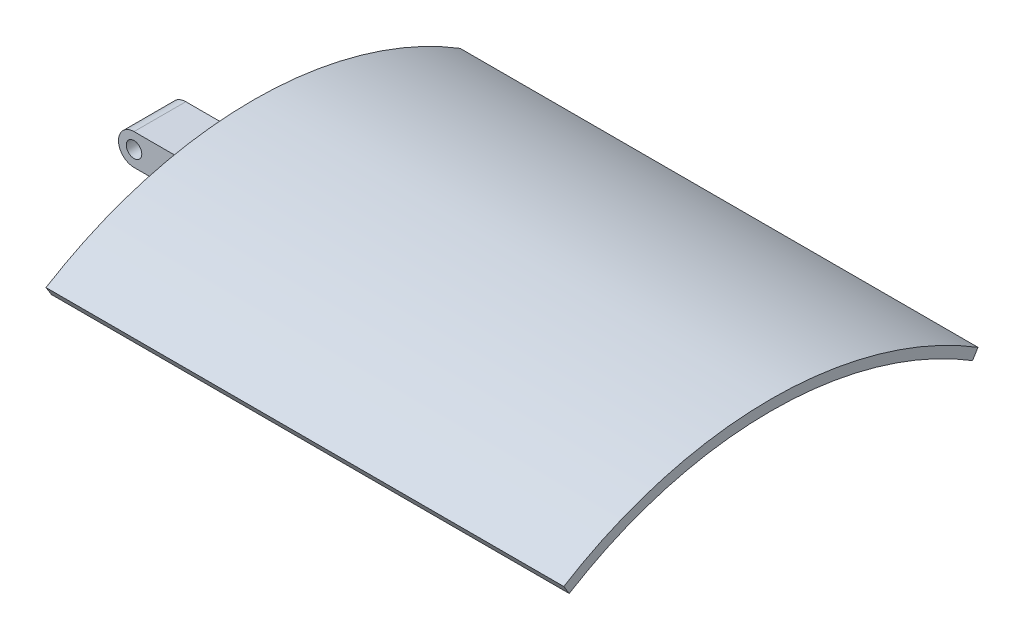
SolidWorks part; units mm, degrees
ref_plane "Plan de face" through (0, 0, 0) normal (0, 0, 1) x (1, 0, 0)
ref_plane "Plan de dessus" through (0, 0, 0) normal (0, 1, 0) x (1, 0, 0)
ref_plane "Plan de droite" through (0, 0, 0) normal (1, 0, 0) x (0, 0, -1)
sketch "Esquisse1" plane through (0, 0, 0) normal (1, 0, 0) x (0, 0, -1)
  line L0 (-40, 64.8571) -> (0, 0) construction
  line L1 (0, 0) -> (40, 64.8571) construction
  line L2 (-40, 64.8571) -> (40, 64.8571) construction
  line L3 (0, 64.8571) -> (0, 0) construction
  line L4 (-40, 64.8571) -> (-38.9501, 63.1548)
  line L5 (40, 64.8571) -> (38.9501, 63.1548)
  arc A0 (-40, 64.8571) -> (40, 64.8571) centre (0, 0) cw
  arc A1 (-38.9501, 63.1548) -> (38.9501, 63.1548) centre (0, 0) cw
  dimension "D1" = 76.2
  dimension "D2" = 63.328
  dimension "D3" = 2
  dimension "D4" = 80
extrude "Boss.-Extru.1" add sketch "Esquisse1" along normal blind 100
sketch "Esquisse3" plane through (0, 0, 0) normal (0, 0, 1) x (1, 0, 0)
  line L0 (60, 74.2) -> (60, 69.2)
  line L1 (100, 74.2) -> (0, 74.2) construction
  line L2 (60, 69.2) -> (66, 69.2) construction
  line L3 (66, 69.2) -> (66, 74.2)
  line L4 (66, 74.2) -> (60, 74.2)
  line L5 (0, 76.2) -> (0, 64.8571) construction
  arc A0 (60, 69.2) -> (66, 69.2) centre (63, 69.2) ccw
  dimension "D1" = 60
  dimension "D2" = 5
  dimension "D3" = 6
extrude "Boss.-Extru.2" add sketch "Esquisse3" along normal blind 3 and the other way blind 3 contours A0 L3 L4 L0
hole_wizard "Dégagement M31" positions "Esquisse4" profile "Esquisse5" hole size "M3" standard "ISO"
sketch "Esquisse4" plane through (0, 0, 3) normal (0, 0, 1) x (1, 0, 0)
  point P0 (63, 69.2)
sketch "Esquisse5" plane through (63, 69.2, 3) normal (1, 0, 0) x (0, -1, 0)
  line L0 (0, 0) -> (0, 9.5215)
  line L1 (0, 9.5215) -> (1.7, 8.5)
  line L2 (1.7, 8.5) -> (1.7, 0)
  line L5 (1.7, 0) -> (0, 0)
  line L10 (0, 9.5215) -> (-1.7, 8.5) construction
  line L11 (0, -6.35) -> (0, 107.95) construction
  dimension "Diamètre du perçage" = 3.4
  dimension "Profondeur du perçage" = 8.5
  dimension "Angle de pointe" = 118
sketch "Esquisse7" plane through (0, 0, 0) normal (0, 0, 1) x (1, 0, 0)
  line L0 (7, 74.2) -> (7, 73.5443)
  line L1 (60, 74.2) -> (0, 74.2) construction
  line L2 (7, 74.2) -> (13, 74.2)
  line L3 (13, 74.2) -> (13, 70.4183)
  line L4 (13, 70.4183) -> (-4.539, 58.4394)
  line L5 (-4.539, 58.4394) -> (-18, 58.4394)
  line L6 (-18, 58.4394) -> (-18, 64.4394) construction
  line L7 (-18, 64.4394) -> (-6.3311, 64.4394)
  line L8 (-6.3311, 64.4394) -> (7, 73.5443)
  line L9 (4.2305, 64.4288) -> (0.3345, 68.9918) construction
  line L10 (10, 74.2) -> (0, 74.2) construction
  line L11 (-18, 61.4394) -> (-6.3311, 61.4394) construction
  line L12 (-6.3311, 61.4394) -> (-6.3311, 64.4394) construction
  line L13 (-6.3311, 61.4394) -> (-6.3311, 58.4394) construction
  circle A0 centre (-18, 61.4394) radius 1.5
  arc A1 (-18, 64.4394) -> (-18, 58.4394) centre (-18, 61.4394) ccw
  point P15 (-4.5238, 60.4394)
  dimension "D3" = 3
  dimension "D1" = 6
  dimension "D2" = 10
  dimension "D4" = 28
  dimension "D5" = 12.7606
extrude "Boss.-Extru.3" add sketch "Esquisse7" along normal blind 5 and the other way blind 5 contours L7 L8 L0 L2 L3 L4 L5 A1 | A0
ref_plane "Plan2" through (0, 61.4394, 0) normal (0, 1, 0) x (1, 0, 0)
